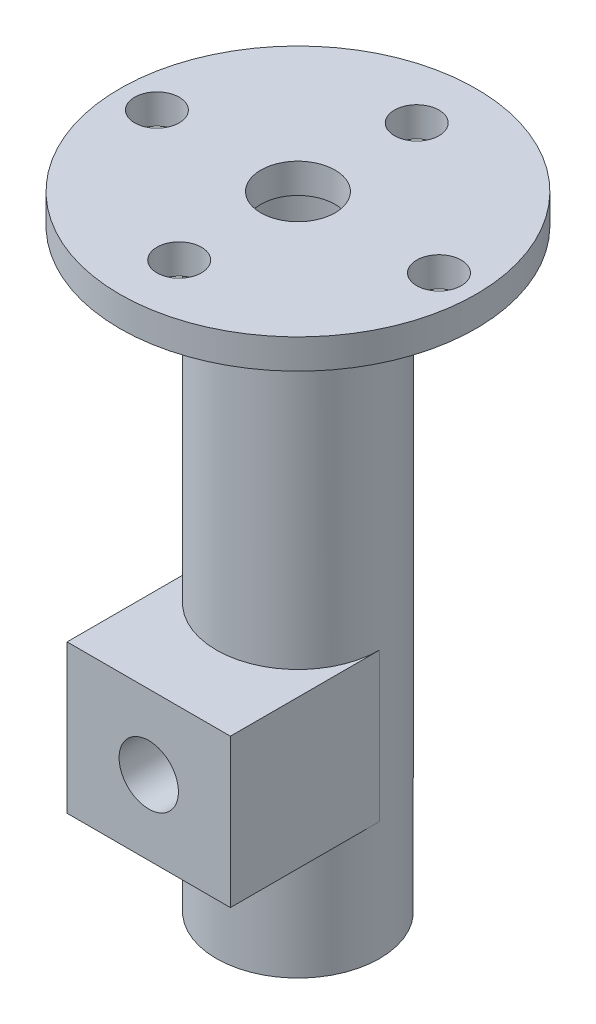
SolidWorks part; units mm, degrees
ref_plane "Front Plane" through (0, 0, 0) normal (0, 0, 1) x (1, 0, 0)
ref_plane "Top Plane" through (0, 0, 0) normal (0, 1, 0) x (1, 0, 0)
ref_plane "Right Plane" through (0, 0, 0) normal (1, 0, 0) x (0, 0, -1)
sketch "Sketch1" plane through (0, 0, 0) normal (0, 1, 0) x (1, 0, 0)
  circle A0 centre (0, 0) radius 14
  circle A1 centre (0, 0) radius 16
  dimension "D1" = 28
  dimension "D2" = 2
extrude "Boss-Extrude1" add sketch "Sketch1" along normal blind 26
sketch "Sketch2" plane through (0, 26, 0) normal (0, 1, 0) x (1, 0, 0)
  circle A0 centre (0, 0) radius 16
  dimension "D1" = 32
extrude "Boss-Extrude2" add sketch "Sketch2" along normal blind 2
sketch "Sketch3" plane through (0, 26, 0) normal (0, -1, 0) x (1, 0, 0)
  line L0 (0, 0) -> (0, 8)
  line L1 (0, 0) -> (9.5, 0)
  circle A0 centre (0, 8) radius 1.5
  circle A1 centre (9.5, 0) radius 1.5
  circle A2 centre (-9.5, 0) radius 1.5
  circle A3 centre (0, -8) radius 1.5
  dimension "D3" = 3
  dimension "D4" = 3
  dimension "D1" = 8
  dimension "D2" = 9.5
extrude "Cut-Extrude1" cut sketch "Sketch3" against normal blind 2 contours A0 | A2 | A3 | A1 region at (-1.0307, 26, 9.0307) region at (9.5, 26, 1.4576) region at (-9.5, 26, 0) region at (0, 26, -8)
sketch "Sketch4" plane through (0, 0, 0) normal (0, -1, 0) x (1, 0, 0)
  line L0 (0, 8) -> (0, -8)
  line L1 (-9.5, 0) -> (9.5, 0)
  line L2 (0, -4.7376) -> (4.7376, 0)
  line L3 (-0.8132, -5.5508) -> (5.5508, 0.8132)
  line L4 (-0.8132, -5.5508) -> (9.7934, -16.1574)
  line L5 (5.5508, 0.8132) -> (16.1574, -9.7934)
  line L6 (9.7934, -16.1574) -> (16.1574, -9.7934)
  point P10 (2.3688, -2.3688)
  point P13 (2.3688, -2.3688)
  circle M8 centre (0, 0) radius 16
  circle M9 centre (0, 0) radius 14
  dimension "D1" = 45
  dimension "D2" = 6.7
  dimension "D3" = 9
  dimension "D4" = 15
extrude "Cut-Extrude2" cut sketch "Sketch4" against normal blind 26 contours L5 L4 M9 M8 region at (10.4425, 0, -10.4425)
sketch "Sketch5" plane through (0, 26, 0) normal (0, -1, 0) x (1, 0, 0)
  circle A0 centre (0, 0) radius 2.5
  dimension "D1" = 5
extrude "Cut-Extrude3" cut sketch "Sketch5" against normal blind 10
sketch "Sketch7" plane through (0, 28, 0) normal (0, 1, 0) x (1, 0, 0)
  line L0 (0, 0) -> (0, 26.5)
  line L1 (0, 0) -> (26.5, 0)
  line L2 (0, 0) -> (0, -26.5)
  line L3 (0, 0) -> (-26.5, 0)
  circle A0 centre (0, 0) radius 16.5
  circle A1 centre (0, 0) radius 26.5
  circle A2 centre (0, 21.5) radius 2.5
  circle A3 centre (21.5, 0) radius 2.5
  circle A4 centre (0, -21.5) radius 2.5
  circle A5 centre (-21.5, 0) radius 2.5
  point P19 (0, 0)
  dimension "D1" = 33
  dimension "D2" = 53
  dimension "D3" = 5
  dimension "D4" = 21.5
  dimension "D5" = 4
sketch "Sketch9" plane through (0, 0, 0) normal (0, -1, 0) x (1, 0, 0)
  circle A0 centre (0, 0) radius 12
  circle A1 centre (0, 0) radius 22.6108
  dimension "D1" = 24
extrude "Cut-Extrude4" cut sketch "Sketch9" against normal blind 44
ref_plane "Plane1" through (0, 6, 0) normal (0, -1, 0) x (-1, 0, 0)
sketch "Sketch10" plane through (0, 26, 0) normal (0, -1, 0) x (1, 0, 0)
  circle A0 centre (0, 0) radius 5.5
  circle A1 centre (0, 0) radius 4.05
  dimension "D1" = 11
  dimension "D2" = 8.1
sketch "Sketch11" plane through (0, 6, 0) normal (0, -1, 0) x (-1, 0, 0)
  circle A0 centre (0, 0) radius 4.05
  circle A1 centre (0, 0) radius 5.5
extrude "Boss-Extrude3" add sketch "Sketch10" along normal blind 40
ref_plane "Plane2" through (0, 0, 4.05) normal (0, 0, 1) x (1, 0, 0)
sketch "Sketch13" plane through (0, 0, 4.05) normal (0, 0, 1) x (1, 0, 0)
  line L0 (-5.5, 26) -> (-5.5, -14) construction
  line L1 (-5.5, -6) -> (5.5, -6)
  line L2 (-5.5, -6) -> (-5.5, 4)
  line L3 (-5.5, 4) -> (5.5, 4)
  line L4 (5.5, -6) -> (5.5, 4)
  line L5 (-5.5, -6) -> (5.5, 4) construction
  line L6 (-5.5, 4) -> (5.5, -6) construction
  line L7 (5.5, -14) -> (5.5, 26) construction
  line L8 (-4.05, 6) -> (4.05, 6) construction
  circle A0 centre (0, -1) radius 2
  point P0 (0, -1)
  dimension "D5" = 4
  dimension "D1" = 0
  dimension "D2" = 0
  dimension "D3" = 10
  dimension "D4" = 12
extrude "Boss-Extrude4" add sketch "Sketch13" along normal blind 6 and the other way blind 4.05
sketch "Sketch14" plane through (0, -14, 0) normal (0, -1, 0) x (1, 0, 0)
  circle A0 centre (0, 0) radius 4.05
extrude "Cut-Extrude5" cut sketch "Sketch14" against normal blind 33
sketch "Sketch15" plane through (0, 0, 10.05) normal (0, 0, 1) x (1, 0, 0)
  circle A0 centre (0, -1) radius 2
extrude "Cut-Extrude6" cut sketch "Sketch15" against normal blind 10
chamfer "Chamfer3" distance 1 angle 45 1 edges at (0, 26, 5.5)
